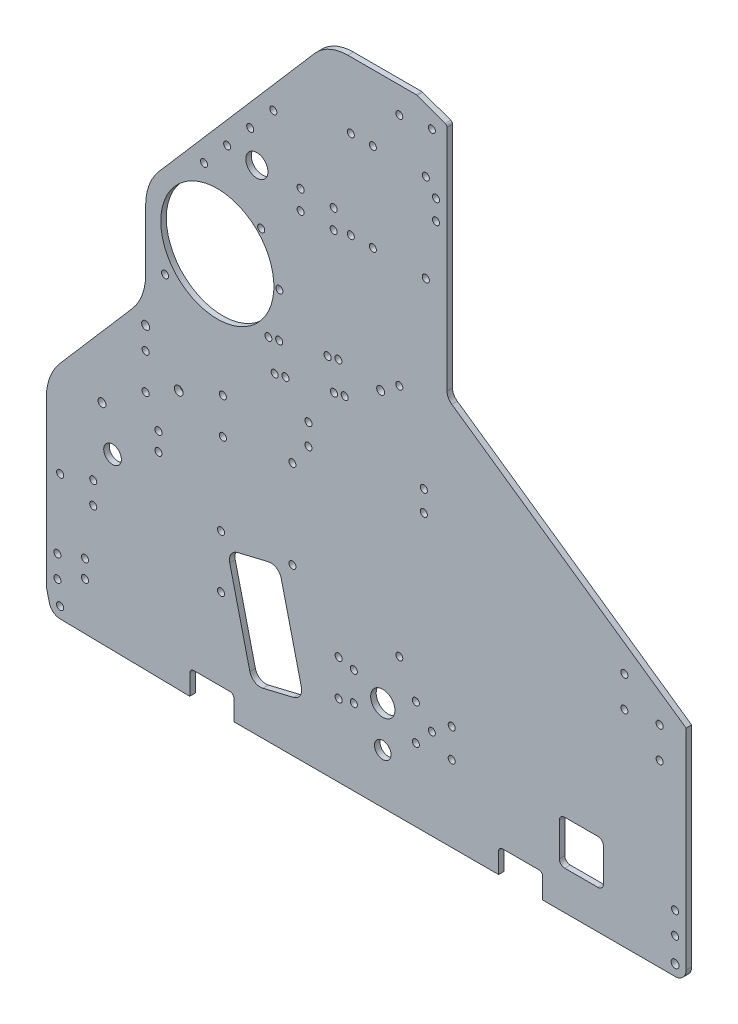
SolidWorks part; units mm, degrees
ref_plane "Front Plane" through (0, 0, 0) normal (0, 0, 1) x (1, 0, 0)
ref_plane "Top Plane" through (0, 0, 0) normal (0, 1, 0) x (1, 0, 0)
ref_plane "Right Plane" through (0, 0, 0) normal (1, 0, 0) x (0, 0, -1)
sketch "Sketch1" plane through (0, 0, 0) normal (0, 0, 1) x (1, 0, 0)
  line L0 (82.55, -20.32) -> (82.55, -6.35)
  line L2 (0, 0) -> (0, 157.48)
  line L4 (368.3, -20.32) -> (368.3, 106.68)
  line L5 (82.55, -6.35) -> (107.95, -6.35)
  line L6 (107.95, -6.35) -> (107.95, -20.32)
  line L7 (107.95, -20.32) -> (260.35, -20.32)
  line L8 (260.35, -20.32) -> (260.35, -6.35)
  line L9 (260.35, -6.35) -> (285.75, -6.35)
  line L10 (285.75, -6.35) -> (285.75, -20.32)
  line L11 (285.75, -20.32) -> (368.3, -20.32)
  line L12 (361.95, 12.7) -> (368.3, 12.7) construction
  line L13 (0, 0) -> (6.35, 0) construction
  line L14 (0.1896, -7.8901) -> (1.7771, -14.2401)
  line L15 (7.8295, -19.0491) -> (82.55, -20.32)
  line L16 (0, 0) -> (0, -6.35)
  line L17 (76.2, 128.905) -> (79.375, 128.905) construction
  line L18 (57.15, 118.5863) -> (101.6, 118.5862) construction
  line L19 (57.15, 118.5863) -> (57.15, 139.2238) construction
  line L20 (101.6, 118.5862) -> (101.6, 139.2237) construction
  line L21 (57.15, 139.2238) -> (101.6, 139.2237) construction
  line L22 (57.15, 118.5863) -> (101.6, 139.2237) construction
  line L23 (101.6, 118.5862) -> (57.15, 139.2238) construction
  line L25 (203.2, 59.805) -> (203.2, 194.805) construction
  line L26 (203.2, 194.805) -> (203.2, 329.805) construction
  line L27 (355.6, 332.105) -> (330.2, 332.105) construction
  line L28 (330.2, 332.105) -> (330.2, 217.805) construction
  line L29 (330.2, 217.805) -> (355.6, 217.805) construction
  line L30 (355.6, 217.805) -> (355.6, 332.105) construction
  line L31 (203.2, 344.805) -> (203.2, 194.805) construction
  line L32 (50.8, 332.105) -> (76.2, 332.105) construction
  line L33 (76.2, 332.105) -> (76.2, 217.805) construction
  line L34 (50.8, 217.805) -> (50.8, 332.105) construction
  line L35 (76.2, 217.805) -> (50.8, 217.805) construction
  line L36 (213.2, 344.805) -> (230.6638, 338.455)
  line L37 (203.2, 344.805) -> (161.925, 344.805)
  line L38 (203.2, 344.805) -> (213.2, 344.805)
  line L39 (348.5362, 344.805) -> (413.4623, 344.805)
  line L40 (348.5362, 344.805) -> (230.6638, 344.805) construction
  line L42 (161.925, 344.805) -> (0, 157.48)
  line L44 (230.6638, 338.455) -> (230.6638, 202.565)
  line L45 (230.6638, 202.565) -> (368.3, 106.68)
  line L46 (213.2, 344.805) -> (-141.0713, 344.805) construction
  circle A0 centre (6.35, 0) radius 2.032
  circle A1 centre (6.35, 12.7) radius 2.032
  circle A2 centre (361.95, 0) radius 2.032
  circle A3 centre (361.95, 12.7) radius 2.032
  arc A5 (1.7771, -14.2401) -> (7.8295, -19.0491) centre (7.9375, -12.7) ccw
  circle A6 centre (7.9375, -12.7) radius 2.032
  arc A7 (0, -6.35) -> (0.1896, -7.8901) centre (6.35, -6.35) ccw
  circle A8 centre (38.1, 78.105) radius 5.08
  circle A9 centre (76.2, 128.905) radius 2.54
  circle A10 centre (101.6, 118.5862) radius 2.032
  circle A11 centre (101.6, 139.2237) radius 2.032
  circle A12 centre (57.15, 139.2238) radius 2.032
  circle A13 centre (57.15, 118.5863) radius 2.032
  circle A15 centre (203.2, 59.805) radius 2
  circle A16 centre (203.2, 194.805) radius 2
  circle A17 centre (203.2, 329.805) radius 2
  circle A18 centre (63.5, 313.055) radius 2.032
  circle A20 centre (355.6, 332.105) radius 2.032
  circle A21 centre (330.2, 332.105) radius 2.032
  circle A22 centre (355.6, 217.805) radius 2.032
  circle A23 centre (330.2, 217.805) radius 2.032
  circle A24 centre (50.8, 332.105) radius 2.032
  circle A25 centre (76.2, 332.105) radius 2.032
  circle A26 centre (50.8, 217.805) radius 2.032
  circle A27 centre (76.2, 217.805) radius 2.032
  circle A28 centre (221.9319, 332.105) radius 2
  circle A29 centre (224.3138, 298.831) radius 2.032
  circle A30 centre (353.06, 100.7351) radius 2.032
  circle A31 centre (332.74, 115.9751) radius 2.032
  circle A32 centre (332.74, 98.1951) radius 2.032
  circle A33 centre (353.06, 82.9551) radius 2.032
  circle A34 centre (117.3562, 280.4276) radius 2.032
  circle A35 centre (104.0678, 265.0548) radius 2.032
  circle A36 centre (90.7795, 249.682) radius 2.032
  circle A38 centre (130.6445, 295.8004) radius 2.032
  circle A39 centre (68.326, 182.9237) radius 2.032
  circle A40 centre (224.3138, 287.401) radius 2.032
  point P82 (203.2, 344.805)
  point P83 (221.9319, 341.63)
  point P90 (368.3, 62.484)
  dimension "D6" = 4.064
  dimension "D10" = 6.35
  dimension "D11" = 4.064
  dimension "D17" = 38.1
  dimension "D27" = 4
  dimension "D31" = 4.064
  dimension "D32" = 41.275
  dimension "D36" = 4.064
  dimension "D47" = 39.624
  dimension "D48" = 4.064
  dimension "D25" = 5.08
  dimension "D26" = 4.064
  dimension "D52" = 4.064
  dimension "D65" = 4.064
  dimension "D69" = 10.16
  dimension "D2" = 127
  dimension "D3" = 13.97
  dimension "D4" = 25.4
  dimension "D5" = 152.4
  dimension "D7" = 12.7
  dimension "D8" = 6.35
  dimension "D9" = 20.32
  dimension "D12" = 12.7
  dimension "D13" = 1.5875
  dimension "D14" = 82.55
  dimension "D15" = 368.3
  dimension "D16" = 6.35
  dimension "D18" = 98.425
  dimension "D19" = 38.1
  dimension "D20" = 50.8
  dimension "D21" = 3.175
  dimension "D22" = 270
  dimension "D23" = 20.6375
  dimension "D24" = 44.45
  dimension "D28" = 135
  dimension "D29" = 12.7
  dimension "D30" = 15
  dimension "D33" = 63.5
  dimension "D34" = 27.4638
  dimension "D35" = 12.7
  dimension "D37" = 114.3
  dimension "D38" = 25.4
  dimension "D39" = 12.7
  dimension "D40" = 157.48
  dimension "D41" = 142.24
  dimension "D42" = 365.125
  dimension "D43" = 10
  dimension "D44" = 6.35
  dimension "D45" = 31.75
  dimension "D46" = 6.35
  dimension "D49" = 6.35
  dimension "D50" = 203.2
  dimension "D51" = 15.24
  dimension "D53" = 17.78
  dimension "D54" = 17.78
  dimension "D55" = 20.32
  dimension "D56" = 15.24
  dimension "D57" = 92.202
  dimension "D58" = 8.382
  dimension "D59" = 20.32
  dimension "D60" = 20.32
  dimension "D61" = 8.382
  dimension "D62" = 20.32
  dimension "D63" = 8.382
  dimension "D64" = 8.382
  dimension "D66" = 35.052
  dimension "D67" = 68.326
  dimension "D68" = 11.43
extrude "Boss-Extrude1" add sketch "Sketch1" along normal blind 3.175 contours L16 A7 L14 A5 L15 L2 A0 A1 A6 region at (171.4477, 119.565, 0)
fillet "Fillet1" radius 2.286 4 edges at (285.75, -6.35, 1.5875) (107.95, -6.35, 1.5875) (260.35, -6.35, 1.5875) (82.55, -6.35, 1.5875)
fillet "Fillet2" radius 6.35 1 edges at (230.6638, 202.565, 1.5875)
sketch "Sketch2" plane through (0, 0, 0) normal (0, 0, -1) x (-1, 0, 0)
  circle A0 centre (-100.5528, 71.086) radius 2.032 construction
  circle A1 centre (-100.5528, 40.606) radius 2.032 construction
  circle A2 centre (-22.225, 18.2025) radius 2.032 construction
  circle A3 centre (-22.225, 8.0425) radius 2.032 construction
  circle A4 centre (-100.5528, 71.086) radius 2.032
  circle A5 centre (-100.5528, 40.606) radius 2.032
  circle A6 centre (-22.225, 18.2025) radius 2.032
  circle A7 centre (-22.225, 8.0425) radius 2.032
extrude "Cut-Extrude1" cut sketch "Sketch2" against normal through all
fillet "Fillet3" radius 1.5875 2 edges at (230.6638, 338.455, 1.5875) (213.2, 344.805, 1.5875)
sketch "Sketch3" plane through (0, 0, 3.175) normal (0, 0, 1) x (1, 0, 0)
  line L0 (132.9524, 63.2646) -> (132.7215, 64.2281) construction
  line L1 (128.3814, 66.8897) -> (110.6828, 62.6472) construction
  line L2 (114.5132, 58.4237) -> (126.8822, 61.3887) construction
  line L3 (108.0212, 58.3071) -> (108.2522, 57.3436) construction
  line L4 (131.2006, 57.703) -> (140.0164, 20.9265) construction
  line L5 (144.0993, 16.7636) -> (132.9524, 63.2646) construction
  line L6 (108.2522, 57.3436) -> (119.3991, 10.8426) construction
  line L7 (121.1509, 16.4042) -> (112.3351, 53.1807) construction
  line L8 (119.3991, 10.8426) -> (119.6301, 9.8791) construction
  line L9 (144.3303, 15.8001) -> (144.0993, 16.7636) construction
  line L10 (137.8383, 15.6835) -> (125.4694, 12.7185) construction
  line L11 (123.9701, 7.2175) -> (141.6687, 11.4601) construction
  line L12 (132.9524, 63.2646) -> (132.7215, 64.2281)
  line L13 (128.3814, 66.8897) -> (110.6828, 62.6472)
  line L14 (114.5132, 58.4237) -> (126.8822, 61.3887)
  line L15 (108.0212, 58.3071) -> (108.2522, 57.3436)
  line L16 (131.2006, 57.703) -> (140.0164, 20.9265)
  line L17 (144.0993, 16.7636) -> (132.9524, 63.2646)
  line L18 (108.2522, 57.3436) -> (119.3991, 10.8426)
  line L19 (121.1509, 16.4042) -> (112.3351, 53.1807)
  line L20 (119.3991, 10.8426) -> (119.6301, 9.8791)
  line L21 (144.3303, 15.8001) -> (144.0993, 16.7636)
  line L22 (137.8383, 15.6835) -> (125.4694, 12.7185)
  line L23 (123.9701, 7.2175) -> (141.6687, 11.4601)
  line L24 (127.7894, 69.3598) -> (110.0908, 65.1172)
  line L25 (105.5512, 57.715) -> (105.7822, 56.7515)
  line L26 (105.7822, 56.7515) -> (116.9291, 10.2505)
  line L27 (116.9291, 10.2505) -> (117.16, 9.287)
  line L28 (124.5622, 4.7475) -> (142.2608, 8.99)
  line L29 (146.8003, 16.3922) -> (146.5694, 17.3557)
  line L30 (146.5694, 17.3557) -> (135.4225, 63.8567)
  line L31 (135.4225, 63.8567) -> (135.1915, 64.8202)
  line L32 (14.605, -0.1369) -> (103.7278, 32.3011) construction
  line L33 (14.605, -0.1369) -> (103.7278, 32.3011)
  line L34 (0, -6.35) -> (0, 157.48) construction
  line L35 (-39.6666, 74.7152) -> (103.7278, 126.9065) construction
  line L36 (26.9875, 46.9531) -> (26.9875, 59.6531) construction
  line L37 (107.95, -20.32) -> (260.35, -20.32) construction
  line L38 (64.5259, 92.5258) -> (64.5259, 102.9405) construction
  arc A0 (132.7215, 64.2281) -> (128.6308, 66.9403) centre (129.2206, 63.3889) ccw construction
  arc A1 (110.6828, 62.6472) -> (110.4377, 62.5791) centre (111.522, 59.1463) ccw construction
  arc A2 (128.6308, 66.9403) -> (128.3814, 66.8897) centre (129.2206, 63.3889) ccw construction
  arc A3 (110.4377, 62.5791) -> (108.0212, 58.3071) centre (111.522, 59.1463) ccw construction
  arc A4 (119.6301, 9.8791) -> (123.7207, 7.1669) centre (123.1309, 10.7183) ccw construction
  arc A5 (141.9139, 11.5281) -> (144.3303, 15.8001) centre (140.8295, 14.9609) ccw construction
  arc A6 (141.6687, 11.4601) -> (141.9139, 11.5281) centre (140.8295, 14.9609) ccw construction
  arc A7 (123.7207, 7.1669) -> (123.9701, 7.2175) centre (123.1309, 10.7183) ccw construction
  arc A8 (132.7215, 64.2281) -> (128.6308, 66.9403) centre (129.2206, 63.3889) ccw
  arc A9 (110.6828, 62.6472) -> (110.4377, 62.5791) centre (111.522, 59.1463) ccw
  arc A10 (128.6308, 66.9403) -> (128.3814, 66.8897) centre (129.2206, 63.3889) ccw
  arc A11 (110.4377, 62.5791) -> (108.0212, 58.3071) centre (111.522, 59.1463) ccw
  arc A12 (119.6301, 9.8791) -> (123.7207, 7.1669) centre (123.1309, 10.7183) ccw
  arc A13 (141.9139, 11.5281) -> (144.3303, 15.8001) centre (140.8295, 14.9609) ccw
  arc A14 (141.6687, 11.4601) -> (141.9139, 11.5281) centre (140.8295, 14.9609) ccw
  arc A15 (123.7207, 7.1669) -> (123.9701, 7.2175) centre (123.1309, 10.7183) ccw
  arc A16 (110.0908, 65.1172) -> (109.6726, 65.0012) centre (111.522, 59.1463) ccw
  arc A17 (109.6726, 65.0012) -> (105.5512, 57.715) centre (111.522, 59.1463) ccw
  arc A18 (117.16, 9.287) -> (124.1369, 4.6613) centre (123.1309, 10.7183) ccw
  arc A19 (124.1369, 4.6613) -> (124.5622, 4.7475) centre (123.1309, 10.7183) ccw
  arc A20 (142.2608, 8.99) -> (142.6789, 9.1061) centre (140.8295, 14.9609) ccw
  arc A21 (142.6789, 9.1061) -> (146.8003, 16.3922) centre (140.8295, 14.9609) ccw
  arc A22 (135.1915, 64.8202) -> (128.2147, 69.446) centre (129.2206, 63.3889) ccw
  arc A23 (128.2147, 69.446) -> (127.7894, 69.3598) centre (129.2206, 63.3889) ccw
  circle A26 centre (134.1438, 208.2281) radius 2.032 construction
  circle A33 centre (26.9875, 46.9531) radius 2.032
  circle A34 centre (26.9875, 59.6531) radius 2.032
  circle A35 centre (7.9375, 53.3031) radius 2.032
  circle A37 centre (32.0306, 100.8109) radius 31.75 construction
  circle A38 centre (32.0306, 100.8109) radius 2.286
  circle A39 centre (123.682, 233.4851) radius 2.032 construction
  circle A40 centre (64.5259, 102.9405) radius 2.032
  circle A41 centre (64.5259, 92.5258) radius 2.032
  circle A42 centre (134.1438, 208.2281) radius 2.032
  circle A43 centre (123.682, 233.4851) radius 2.032
  ellipse E0 centre (124.5974, 48.8487) end of major axis (128.5376, 61.3578) minor radius 6 (131.2006, 57.703) -> (126.8822, 61.3887) ccw construction
  ellipse E1 centre (122.2349, 48.2824) end of major axis (113.0518, 57.6456) minor radius 6 (114.5132, 58.4237) -> (112.3351, 53.1807) ccw construction
  ellipse E2 centre (127.7541, 25.2585) end of major axis (131.6942, 37.7675) minor radius 6 (121.1509, 16.4042) -> (125.4694, 12.7185) ccw construction
  ellipse E3 centre (130.1166, 25.8248) end of major axis (139.2998, 16.4616) minor radius 6 (137.8383, 15.6835) -> (140.0164, 20.9265) ccw construction
  ellipse E4 centre (124.5974, 48.8487) end of major axis (128.5376, 61.3578) minor radius 6 (131.2006, 57.703) -> (126.8822, 61.3887) ccw
  ellipse E5 centre (122.2349, 48.2824) end of major axis (131.4181, 38.9192) minor radius 6 (114.5132, 58.4237) -> (112.3351, 53.1807) ccw
  ellipse E6 centre (127.7541, 25.2585) end of major axis (123.8139, 12.7495) minor radius 6 (121.1509, 16.4042) -> (125.4694, 12.7185) ccw
  ellipse E7 centre (130.1166, 25.8248) end of major axis (139.2998, 16.4616) minor radius 6 (137.8383, 15.6835) -> (140.0164, 20.9265) ccw
  point P93 (26.9875, 53.3031)
  point P115 (32.0306, 100.8109)
  dimension "D3" = 63.5
  dimension "D4" = 4.572
  dimension "D8" = 4.064
  dimension "D2" = 88.9
  dimension "D5" = 7.9375
  dimension "D6" = 19.05
  dimension "D7" = 73.6231
  dimension "D9" = 12.7
  dimension "D10" = 10.4147
  dimension "D11" = 37.5384
  dimension "D12" = 45.5727
  dimension "D1" = 2.54
extrude "Cut-Extrude2" cut sketch "Sketch3" against normal through all contours A22 A23 L24 A16 A17 L25 L26 L27 A18 A19 L28 A20 A21 L29 L30 L31 A15 A12 L20 L18 L15 A11 A9 L13 A10 A8 L12 L17 L21 A13 A14 L23 | A12 A15 L23 A14 A13 L21 L17 L12 A8 A10 L13 A9 A11 L15 L18 L20 E7 L22 E6 L19 E5 L14 E4 L16 | L22 E7 L16 E4 L14 E5 L19 E6 | A38 | A41 | A40 | A35 | A34 | A33 | A43 | A42 region at (137.844, 39.8506, 3.175) region at (126.1758, 37.0536, 3.175) region at (128.1544, 68.6507, 3.175) region at (32.0306, 100.8109, 3.175) region at (64.5259, 102.9405, 3.175) region at (64.5259, 92.5258, 3.175)
sketch "Sketch4" plane through (0, 0, 3.175) normal (0, 0, 1) x (1, 0, 0)
  line L0 (57.15, 139.2238) -> (101.6, 139.2237) construction
  line L1 (168.275, 21.4312) -> (212.725, 21.4312) construction
  line L2 (168.275, 21.4312) -> (168.275, 42.0687) construction
  line L3 (168.275, 42.0687) -> (212.725, 42.0687) construction
  line L4 (212.725, 21.4312) -> (212.725, 42.0687) construction
  line L5 (168.275, 21.4312) -> (212.725, 42.0687) construction
  line L6 (168.275, 42.0687) -> (212.725, 21.4312) construction
  line L7 (57.15, 118.5863) -> (57.15, 139.2238) construction
  line L8 (107.95, -20.32) -> (260.35, -20.32) construction
  line L9 (193.675, 31.75) -> (177.005, 31.75) construction
  line L10 (190.5, 31.75) -> (193.675, 31.75) construction
  line L11 (6.35, 12.7) -> (361.95, 12.7) construction
  line L12 (107.95, -6.35) -> (107.95, -20.32) construction
  line L13 (193.675, 31.75) -> (220.6625, 31.75) construction
  line L14 (177.005, 23.4569) -> (177.005, 40.0431) construction
  line L15 (213.2, 44.805) -> (193.2, 44.805) construction
  line L16 (213.2, 44.805) -> (213.2, 344.805) construction
  line L17 (213.2, 344.805) -> (193.2, 344.805) construction
  line L18 (193.2, 44.805) -> (193.2, 344.805) construction
  line L19 (213.2, 44.805) -> (193.2, 344.805) construction
  line L20 (213.2, 344.805) -> (193.2, 44.805) construction
  line L21 (226.9319, 332.105) -> (226.9319, 31.75) construction
  line L22 (237.33, 40.0431) -> (233.3612, 40.0431) construction
  line L23 (237.33, 23.4569) -> (233.3612, 23.4569) construction
  circle A0 centre (168.275, 42.0687) radius 2.032
  circle A1 centre (212.725, 42.0687) radius 2.032
  circle A2 centre (212.725, 21.4312) radius 2.032
  circle A3 centre (168.275, 21.4312) radius 2.032
  circle A4 centre (193.675, 31.75) radius 6.985
  circle A7 centre (220.6625, 31.75) radius 14.2875 construction
  circle A8 centre (193.675, 31.75) radius 12.7 construction
  circle A9 centre (177.005, 40.0431) radius 2.032
  circle A10 centre (177.005, 23.4569) radius 2.032
  circle A11 centre (237.33, 40.0431) radius 2.032 construction
  circle A12 centre (237.33, 23.4569) radius 2.032 construction
  circle A13 centre (193.675, 8.4667) radius 4.7625
  circle A14 centre (221.9319, 31.75) radius 2.032
  circle A15 centre (221.9319, 31.75) radius 5 construction
  circle A16 centre (221.9319, 332.105) radius 5 construction
  circle A17 centre (233.3612, 23.4569) radius 2.032
  circle A18 centre (233.3612, 40.0431) radius 2.032
  point P0 (190.5, 31.75)
  point P26 (203.2, 194.805)
  point P38 (177.005, 31.75)
  dimension "D1" = 4.064
  dimension "D4" = 13.97
  dimension "D7" = 9.525
  dimension "D10" = 25.4
  dimension "D11" = 28.575
  dimension "D16" = 10
  dimension "D17" = 4.064
  dimension "D18" = 10
  dimension "D2" = 52.07
  dimension "D3" = 3.175
  dimension "D5" = 82.55
  dimension "D6" = 26.9875
  dimension "D8" = 20
  dimension "D9" = 300
  dimension "D12" = 16.67
  dimension "D13" = 16.5862
  dimension "D14" = 60.325
  dimension "D15" = 23.2833
  dimension "D19" = 3.9688
extrude "Cut-Extrude3" cut sketch "Sketch4" against normal through all
sketch "Sketch5" plane through (0, 0, 0) normal (0, 0, -1) x (-1, 0, 0)
  line L0 (-57.15, 223.5947) -> (-57.15, 165.3337)
  line L1 (-161.925, 344.805) -> (-52.7201, 218.4699) construction
  line L2 (-57.15, 165.3337) -> (0, 99.219)
  line L3 (0, -6.35) -> (0, 157.48) construction
  line L5 (-50.4199, 215.8089) -> (0, 157.48) construction
  line L6 (-57.15, 223.5947) -> (0, 157.48)
  line L7 (0, 157.48) -> (0, 99.219)
  line L8 (-361.95, -13.97) -> (-368.3, -13.97) construction
  line L9 (-361.95, -13.97) -> (-361.95, -20.32) construction
  line L10 (-285.75, -20.32) -> (-368.3, -20.32) construction
  line L11 (-368.3, -20.32) -> (-368.3, 106.68) construction
  circle A0 centre (-98.425, 208.2281) radius 32.5437
  circle A2 centre (-361.95, -13.97) radius 2.286
  dimension "D3" = 65.0875
  dimension "D7" = 4.572
  dimension "D1" = 38.1
  dimension "D2" = 57.15
  dimension "D4" = 41.275
  dimension "D5" = 41.275
  dimension "D6" = 6.35
extrude "Cut-Extrude5" cut sketch "Sketch5" against normal through all contours A0 | L7 L6 L0 L2 | A2 region at (28.575, 161.4068, 0) region at (98.425, 208.2281, 0)
fillet "Fillet4" radius 31.75 3 edges at (0, 99.219, 1.5875) (57.15, 165.3337, 1.5875) (57.15, 223.5947, 1.5875)
sketch "Sketch6" plane through (0, 0, 3.175) normal (0, 0, 1) x (1, 0, 0)
  line L0 (285.75, -20.32) -> (368.3, -20.32) construction
  line L1 (298.45, 27.305) -> (317.5, 27.305)
  line L2 (295.275, 24.13) -> (295.275, 5.08)
  line L3 (298.45, 1.905) -> (317.5, 1.905)
  line L4 (320.675, 24.13) -> (320.675, 5.08)
  line L5 (295.275, 27.305) -> (320.675, 1.905) construction
  line L6 (295.275, 1.905) -> (320.675, 27.305) construction
  line L7 (368.3, -20.32) -> (368.3, 106.68) construction
  arc A0 (295.275, 5.08) -> (298.45, 1.905) centre (298.45, 5.08) ccw
  arc A1 (317.5, 1.905) -> (320.675, 5.08) centre (317.5, 5.08) ccw
  arc A2 (317.5, 27.305) -> (320.675, 24.13) centre (317.5, 24.13) cw
  arc A3 (298.45, 27.305) -> (295.275, 24.13) centre (298.45, 24.13) ccw
  point P0 (307.975, 14.605)
  dimension "D2" = 3.175
  dimension "D1" = 25.4
  dimension "D3" = 22.225
  dimension "D4" = 47.625
extrude "Cut-Extrude6" cut sketch "Sketch6" against normal through all
fillet "Fillet5" radius 25.4 1 edges at (161.925, 344.805, 1.5875)
sketch "Sketch8" plane through (0, 0, 0) normal (0, 0, -1) x (-1, 0, 0)
  line L0 (-230.6638, 337.343) -> (-230.6638, 205.8802) construction
  line L1 (-230.6638, 255.905) -> (-175.26, 255.905) construction
  line L2 (-175.26, 255.905) -> (-175.26, 306.705) construction
  line L3 (-175.26, 306.705) -> (-230.6638, 306.705) construction
  line L4 (-173.5432, 344.805) -> (-212.9203, 344.805) construction
  circle A8 centre (-187.96, 306.705) radius 2.032
  circle A11 centre (-205.74, 306.705) radius 2.032
  circle A13 centre (-205.74, 255.905) radius 2.032
  circle A14 centre (-187.96, 255.905) radius 2.032
  circle A16 centre (-218.44, 306.705) radius 2.032
  circle A17 centre (-175.26, 306.705) radius 2.032
  circle A18 centre (-175.26, 255.905) radius 2.032
  circle A19 centre (-218.44, 255.905) radius 2.032
  circle A20 centre (-218.44, 306.705) radius 3.9687
  circle A21 centre (-205.74, 306.705) radius 3.9687
  circle A22 centre (-175.26, 306.705) radius 3.9687
  circle A23 centre (-218.44, 255.905) radius 3.9688
  circle A24 centre (-205.74, 255.905) radius 3.9688
  circle A25 centre (-187.96, 255.905) radius 3.9688
  circle A26 centre (-175.26, 255.905) radius 3.9688
  circle A27 centre (-187.96, 306.705) radius 3.9687
  dimension "D1" = 7.9375
  dimension "D7" = 4.064
  dimension "D2" = 12.2237
  dimension "D3" = 12.7
  dimension "D4" = 17.78
  dimension "D5" = 12.7
  dimension "D6" = 88.9
  dimension "D8" = 38.1
  dimension "D9" = 17.78
  dimension "D10" = 12.7
  dimension "D11" = 55.4037
  dimension "D12" = 12.7
extrude "Cut-Extrude7" cut sketch "Sketch8" against normal through all contours A16 | A17 | A18 | A19 | A8 | A14 region at (218.44, 306.705, 0) region at (175.26, 306.705, 0) region at (175.26, 255.905, 0) region at (218.44, 255.905, 0)
sketch "Sketch10" plane through (0, 0, 3.175) normal (0, 0, 1) x (1, 0, 0)
  circle A4 centre (141.6425, 74.6844) radius 2.032 construction
  circle A5 centre (141.6425, 125.4844) radius 2.032 construction
  circle A6 centre (141.6425, 74.6844) radius 2.032
  circle A7 centre (141.6425, 125.4844) radius 2.032
extrude "Cut-Extrude8" cut sketch "Sketch10" against normal through all
fillet "Fillet6" radius 6.35 1 edges at (368.3, -20.32, 1.5875)
sketch "Sketch11" plane through (0, 0, 3.175) normal (0, 0, 1) x (1, 0, 0)
  ellipse E4 centre (150.8814, 138.43) end of major axis (150.8814, 140.462) minor radius 2.032
  ellipse E5 centre (150.8814, 150.495) end of major axis (150.8814, 152.527) minor radius 2.032
  ellipse E6 centre (217.3024, 150.495) end of major axis (217.3024, 152.527) minor radius 2.032
  ellipse E7 centre (217.3024, 138.43) end of major axis (217.3024, 140.462) minor radius 2.032
extrude "Cut-Extrude9" cut sketch "Sketch11" against normal through all
sketch "Sketch12" plane through (0, 0, 0) normal (0, 0, -1) x (-1, 0, 0)
  line L0 (-173.5432, 344.805) -> (-212.9203, 344.805) construction
  circle A0 centre (-165.4175, 264.635) radius 2.032
  circle A1 centre (-203.2, 329.805) radius 2 construction
  circle A2 centre (-165.4175, 253.5225) radius 2.032
  circle A3 centre (-146.3675, 253.5225) radius 2.032
  circle A4 centre (-146.3675, 264.635) radius 2.032
  dimension "D1" = 80.17
  dimension "D2" = 4.064
  dimension "D3" = 37.7825
  dimension "D4" = 11.1125
  dimension "D5" = 19.05
extrude "Cut-Extrude10" cut sketch "Sketch12" against normal through all
sketch "Sketch13" plane through (0, 0, 0) normal (0, 0, -1) x (-1, 0, 0)
  line L0 (-190.2532, 261.8265) -> (-167.7107, 270.5564)
  line L1 (-140.0175, 264.635) -> (-140.0175, 253.5225)
  line L2 (-166.0849, 247.2077) -> (-188.6274, 249.5902)
  line L3 (-165.4175, 247.1725) -> (-146.3675, 247.1725)
  line L4 (-165.4175, 270.985) -> (-146.3675, 270.985)
  circle A0 centre (-146.3675, 264.635) radius 2.032 construction
  circle A1 centre (-146.3675, 253.5225) radius 2.032 construction
  circle A2 centre (-165.4175, 253.5225) radius 2.032 construction
  circle A3 centre (-165.4175, 264.635) radius 2.032 construction
  circle A4 centre (-175.26, 255.905) radius 2.032 construction
  circle A5 centre (-187.96, 255.905) radius 2.032 construction
  circle A6 centre (-146.3675, 264.635) radius 2.032
  circle A7 centre (-146.3675, 253.5225) radius 2.032
  circle A8 centre (-165.4175, 253.5225) radius 2.032
  circle A9 centre (-165.4175, 264.635) radius 2.032
  circle A10 centre (-175.26, 255.905) radius 2.032
  circle A11 centre (-187.96, 255.905) radius 2.032
  arc A12 (-188.6274, 249.5902) -> (-190.2532, 261.8265) centre (-187.96, 255.905) cw
  arc A13 (-167.7107, 270.5564) -> (-165.4175, 270.985) centre (-165.4175, 264.635) cw
  arc A14 (-166.0849, 247.2077) -> (-165.4175, 247.1725) centre (-165.4175, 253.5225) ccw
  arc A15 (-146.3675, 247.1725) -> (-140.0175, 253.5225) centre (-146.3675, 253.5225) ccw
  arc A16 (-146.3675, 270.985) -> (-140.0175, 264.635) centre (-146.3675, 264.635) cw
  dimension "D1" = 6.35
extrude "Boss-Extrude2" [suppressed] add sketch "Sketch13" along normal blind 6.35 separate body
sketch "Sketch14" plane through (0, 0, 0) normal (0, 0, -1) x (-1, 0, 0)
  line L0 (-130.6445, 295.8004) -> (-121.1847, 263.6885) construction
  line L1 (-121.1847, 263.6885) -> (-90.7795, 249.682) construction
  line L2 (-154.3272, 336.0154) -> (-64.88, 232.5373) construction
  line L4 (-118.517, 269.4796) -> (-115.3937, 261.0208) construction
  line L5 (-118.517, 269.4796) -> (-126.9758, 266.3562) construction
  line L6 (-126.9758, 266.3562) -> (-123.8524, 257.8974) construction
  line L7 (-115.3937, 261.0208) -> (-123.8524, 257.8974) construction
  line L8 (-118.517, 269.4796) -> (-123.8524, 257.8974) construction
  line L9 (-126.9758, 266.3562) -> (-115.3937, 261.0208) construction
  circle A0 centre (-121.1847, 263.6885) radius 6.376
  dimension "D1" = 22.225
  dimension "D2" = 9.017
extrude "Cut-Extrude11" cut sketch "Sketch14" against normal through all
sketch "Sketch15" plane through (0, 0, 3.175) normal (0, 0, 1) x (1, 0, 0)
  line L1 (27.1508, 77.7471) -> (81.7263, 77.7471) construction
  line L2 (57.15, 139.2238) -> (57.15, 151.9238) construction
  line L3 (27.1508, 77.7471) -> (52.3291, 153.5255) construction
  line L4 (56.0505, 156.8833) -> (192.439, 187.1199) construction
  circle A0 centre (27.1508, 77.7471) radius 2.159 construction
  circle A1 centre (27.1508, 77.7471) radius 2.159 construction
  circle A2 centre (57.15, 139.2238) radius 2.032 construction
  circle A3 centre (57.15, 139.2238) radius 2.032 construction
  circle A4 centre (57.15, 151.9238) radius 2.286
  circle A5 centre (192.439, 187.1199) radius 2.286
  circle A6 centre (57.15, 151.9238) radius 5.08 construction
  arc A9 (163.8737, 173.6806) -> (164.5125, 170.7993) centre (165.557, 172.5423) ccw construction
  arc A10 (173.4398, 172.7784) -> (172.801, 175.6597) centre (171.7565, 173.9167) ccw construction
  arc A11 (172.801, 175.6597) -> (173.4398, 172.7784) centre (171.7565, 173.9167) ccw construction
  arc A12 (164.5125, 170.7993) -> (163.8737, 173.6806) centre (165.557, 172.5423) ccw construction
  arc A13 (169.1589, 192.0883) -> (169.7976, 189.2071) centre (168.1143, 190.3453) ccw construction
  arc A14 (169.7976, 189.2071) -> (169.1589, 192.0883) centre (168.1143, 190.3453) ccw construction
  arc A15 (160.2316, 190.1092) -> (160.8704, 187.2279) centre (161.9149, 188.9709) ccw construction
  arc A16 (160.8704, 187.2279) -> (160.2316, 190.1092) centre (161.9149, 188.9709) ccw construction
  arc A17 (129.7766, 166.1214) -> (130.4154, 163.2402) centre (131.4599, 164.9832) ccw construction
  arc A18 (139.3426, 165.2193) -> (138.7039, 168.1005) centre (137.6593, 166.3576) ccw construction
  arc A19 (138.7039, 168.1005) -> (139.3426, 165.2193) centre (137.6593, 166.3576) ccw construction
  arc A20 (130.4154, 163.2402) -> (129.7766, 166.1214) centre (131.4599, 164.9832) ccw construction
  arc A21 (135.7005, 181.6479) -> (135.0617, 184.5292) centre (134.0172, 182.7862) ccw construction
  arc A22 (135.0617, 184.5292) -> (135.7005, 181.6479) centre (134.0172, 182.7862) ccw construction
  arc A23 (126.1345, 182.55) -> (126.7732, 179.6688) centre (127.8177, 181.4118) ccw construction
  arc A24 (126.7732, 179.6688) -> (126.1345, 182.55) centre (127.8177, 181.4118) ccw construction
  arc A25 (163.8737, 173.6806) -> (164.5125, 170.7993) centre (165.557, 172.5423) ccw
  arc A26 (173.4398, 172.7784) -> (172.801, 175.6597) centre (171.7565, 173.9167) ccw
  arc A27 (172.801, 175.6597) -> (173.4398, 172.7784) centre (171.7565, 173.9167) ccw
  arc A28 (164.5125, 170.7993) -> (163.8737, 173.6806) centre (165.557, 172.5423) ccw
  arc A29 (169.1589, 192.0883) -> (169.7976, 189.2071) centre (168.1143, 190.3453) ccw
  arc A30 (169.7976, 189.2071) -> (169.1589, 192.0883) centre (168.1143, 190.3453) ccw
  arc A31 (160.2316, 190.1092) -> (160.8704, 187.2279) centre (161.9149, 188.9709) ccw
  arc A32 (160.8704, 187.2279) -> (160.2316, 190.1092) centre (161.9149, 188.9709) ccw
  arc A33 (129.7766, 166.1214) -> (130.4154, 163.2402) centre (131.4599, 164.9832) ccw
  arc A34 (139.3426, 165.2193) -> (138.7039, 168.1005) centre (137.6593, 166.3576) ccw
  arc A35 (138.7039, 168.1005) -> (139.3426, 165.2193) centre (137.6593, 166.3576) ccw
  arc A36 (130.4154, 163.2402) -> (129.7766, 166.1214) centre (131.4599, 164.9832) ccw
  arc A37 (135.7005, 181.6479) -> (135.0617, 184.5292) centre (134.0172, 182.7862) ccw
  arc A38 (135.0617, 184.5292) -> (135.7005, 181.6479) centre (134.0172, 182.7862) ccw
  arc A39 (126.1345, 182.55) -> (126.7732, 179.6688) centre (127.8177, 181.4118) ccw
  arc A40 (126.7732, 179.6688) -> (126.1345, 182.55) centre (127.8177, 181.4118) ccw
  dimension "D2" = 4.572
  dimension "D6" = 10.16
  dimension "D1" = 12.7
  dimension "D3" = 139.7
  dimension "D4" = 12.5
extrude "Cut-Extrude12" cut sketch "Sketch15" against normal through all
